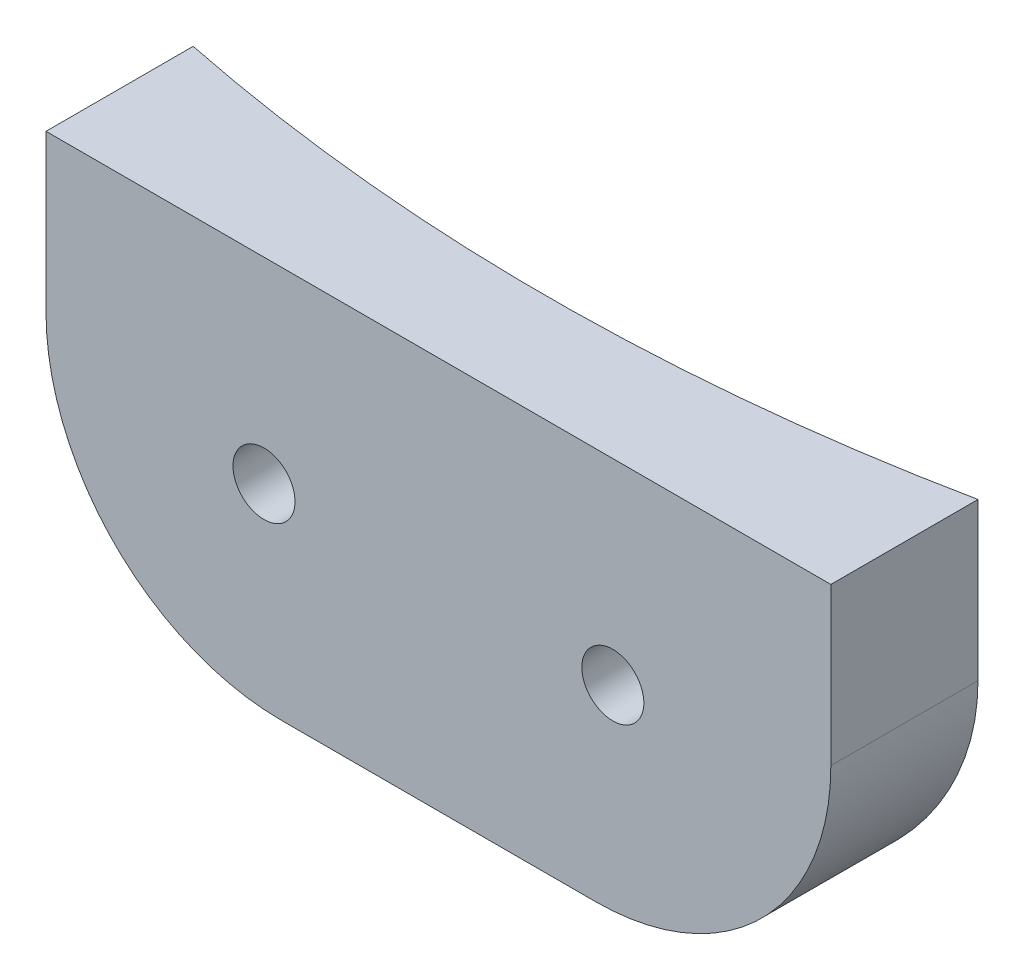
SolidWorks part; units mm, degrees
material "6061 Alloy"
ref_plane "Front Plane" through (0, 0, 0) normal (0, 0, 1) x (1, 0, 0)
ref_plane "Top Plane" through (0, 0, 0) normal (0, 1, 0) x (1, 0, 0)
ref_plane "Right Plane" through (0, 0, 0) normal (1, 0, 0) x (0, 0, -1)
sketch "Sketch1" plane through (0, 0, 0) normal (0, 1, 0) x (1, 0, 0)
  line L0 (-12.7, -62.217) -> (-12.7, -65.4543)
  line L1 (12.7, -62.217) -> (12.7, -65.4543)
  line L2 (-12.7, -66.9795) -> (12.7, -66.9795)
  line L3 (-12.7, -65.4543) -> (-12.7, -66.9795)
  line L4 (12.7, -65.4543) -> (12.7, -66.9795)
  circle A0 centre (0, 0) radius 63.5
  circle A1 centre (0, 0) radius 66.675
  dimension "D1" = 127
  dimension "D3" = 12.7
  dimension "D4" = 12.7
  dimension "D5" = 4.7625
  dimension "D2" = 3.175
extrude "Boss-Extrude1" add sketch "Sketch1" along normal blind 12.7 contours L0 A1 L1 A0 | A1 L3 L2 | A1 L2 L4 region at (0, 0, 64.6697) region at (0, 0, 66.9295)
sketch "Sketch2" plane through (0, 0, 0) normal (0, 0, 1) x (1, 0, 0)
  line L0 (0, 12.7) -> (0, 0) construction
  line L5 (-12.7, 0) -> (12.7, 0)
  line L6 (12.7, 0) -> (12.7, 12.7)
  line L7 (12.7, 12.7) -> (-12.7, 12.7)
  line L12 (-12.7, 12.7) -> (-12.7, 0)
  line L13 (-12.7, 0) -> (12.7, 0)
  line L14 (12.7, 0) -> (12.7, 12.7)
  line L15 (12.7, 12.7) -> (-12.7, 12.7)
  line L16 (-12.7, 12.7) -> (-12.7, 0)
  circle A0 centre (-5.6444, 6.35) radius 1.0033
  dimension "D6" = 2.0066
  dimension "D5" = 5.6444
  dimension "D2" = 6.35
extrude "Cut-Extrude1" cut sketch "Sketch2" along normal up to surface (66.9795 mm away) contours A0 up to face at (0, 6.35, 66.9795)
mirror "Mirror1" about plane through (0, 0, 0) normal (1, 0, 0) of "Cut-Extrude1"
fillet "Fillet1" radius 7.62 2 edges at (-12.7, 0, 64.5983) (12.7, 0, 64.5983)
equation "\"Middle Coupler Inner Daimeter\"= 4.5in"
equation "\"Middle Coupler  Wall Thickness\" = 0.25in"
equation "\"Middle Coupler Bottom Thickness\"= 0.2in"
equation "\"Bearing Rail Offset\"= 0.45in"
equation "\"3-56 UNF Tap\"= 0.089in"
equation "\"3-56 UNF Clearance\"= 0.104in"
equation "\"Ball Bearing Distance\"= 0.03in"
equation "\"TCA Outer Diameter\" = 6.625in"
equation "\"D1@Sketch1\"=\"Middle Coupler Inner Daimeter\"+0.5"
equation "\"D2@Sketch1\"=1/8"
equation "\"D3@Sketch1\"=0.5"
equation "\"D4@Sketch1\"=\"D3@Sketch1\""
equation "\"D6@Sketch2\"=\"3-48 Tap\""
equation "\"Interstage Aeroframe Wall Thickness\" = 0.072in"
equation "\"Compression Spring OD\"= 0.42in"
equation "\"10-24 Tap\"= 0.157in"
equation "\"10-24 Clearance\"= 0.196in"
equation "\"Lower Stage Fuselage Wall Thickness\" = 0.25in"
equation "\"6-32 Tap\" = 0.107in"
equation "\"1/4-20 Tap\" = 0.201in"
equation "\"3-48 Tap\"= 0.079in"
equation "\"3-48 Clearance\" = 0.104in"
equation "\"6-32 Clearance\" = 0.144"
equation "\"12-24 Tap\" = 0.177in"
equation "\"D5@Sketch1\"=3/16"
